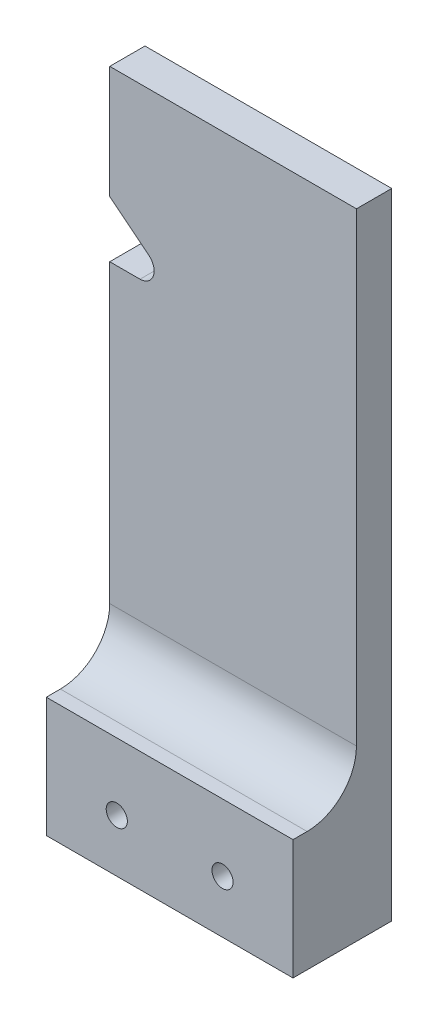
SolidWorks part; units mm, degrees
ref_plane "前视基准面" through (0, 0, 0) normal (0, 0, 1) x (1, 0, 0)
ref_plane "上视基准面" through (0, 0, 0) normal (0, 1, 0) x (1, 0, 0)
ref_plane "右视基准面" through (0, 0, 0) normal (1, 0, 0) x (0, 0, -1)
other "Configuration Table"
sketch "草图1" plane through (0, 0, 0) normal (0, 0, 1) x (1, 0, 0)
  line L1 (-17.5, -45) -> (17.5, -45)
  line L2 (-17.5, -45) -> (-17.5, 45)
  line L3 (-17.5, 45) -> (17.5, 45)
  line L4 (17.5, -45) -> (17.5, 45)
  line L5 (-17.5, -45) -> (17.5, 45) construction
  line L6 (-17.5, 45) -> (17.5, -45) construction
  point P0 (0, 0)
  dimension "D1" = 90
  dimension "D2" = 35
extrude "凸台-拉伸1" add sketch "草图1" along normal blind 5
sketch "草图2" plane through (0, 0, 5) normal (0, 0, 1) x (1, 0, 0)
  line L0 (17.5, -45) -> (17.5, 45) construction
  line L1 (-17.5, -45) -> (17.5, -45)
  line L2 (-17.5, -45) -> (-17.5, -28)
  line L3 (-17.5, -28) -> (17.5, -28)
  line L4 (17.5, -45) -> (17.5, -28)
  dimension "D1" = 17
extrude "凸台-拉伸2" add sketch "草图2" along normal blind 9
fillet "圆角1" radius 7 1 edges at (0, -28, 5)
sketch "草图3" plane through (0, 0, 14) normal (0, 0, 1) x (1, 0, 0)
  line L0 (-17.5, -28) -> (-17.5, -45) construction
  line L1 (17.5, -45) -> (17.5, -28) construction
  line L2 (-17.5, -45) -> (17.5, -45) construction
  circle A0 centre (-7.5, -37.5) radius 1.5
  circle A1 centre (7.5, -37.5) radius 1.5
  dimension "D1" = 3
  dimension "D2" = 3
  dimension "D3" = 10
  dimension "D4" = 10
  dimension "D5" = 7.5
  dimension "D6" = 7.5
extrude "切除-拉伸3" cut sketch "草图3" against normal through all
sketch "草图4" plane through (0, 0, 0) normal (0, 0, -1) x (-1, 0, 0)
  line L5 (17.5, 21) -> (7.5, 21)
  line L6 (17.5, 45) -> (17.5, -45) construction
  line L7 (7.5, 21) -> (17.5, 29)
  line L8 (17.5, 29) -> (17.5, 21)
  line L9 (-17.5, 45) -> (17.5, 45) construction
  dimension "D4" = 16
  dimension "D5" = 8
  dimension "D6" = 10
extrude "切除-拉伸4" cut sketch "草图4" against normal through all
fillet "圆角2" radius 2 1 edges at (-7.5, 21, 2.5)
